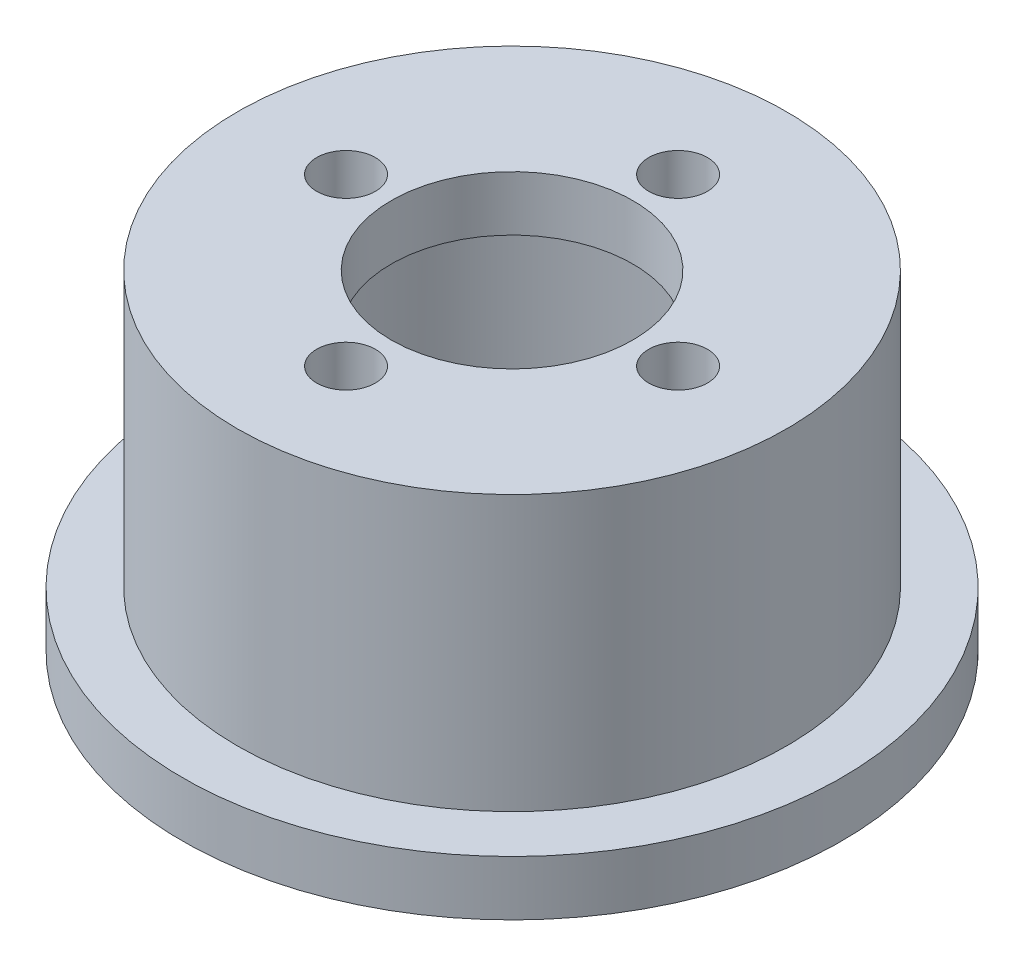
SolidWorks part; units mm, degrees
other "Markup1"
sketch "Sketch5" plane through (-30, 25, 30) normal (-0.0255, 0.5913, 0.806) x (0.9947, 0.0957, -0.0387)
ref_plane "Front Plane" through (0, 0, 0) normal (0, 0, 1) x (1, 0, 0)
ref_plane "Top Plane" through (0, 0, 0) normal (0, 1, 0) x (1, 0, 0)
ref_plane "Right Plane" through (0, 0, 0) normal (1, 0, 0) x (0, 0, -1)
sketch "Sketch1" plane through (0, 0, 0) normal (0, 1, 0) x (1, 0, 0)
  circle A0 centre (0, 0) radius 25
  circle A1 centre (0, 0) radius 20
  dimension "D2" = 50
  dimension "D1" = 40
extrude "Boss-Extrude1" add sketch "Sketch1" along normal blind 20
ref_plane "Plane1" through (0, 20, 0) normal (0, 1, 0) x (1, 0, 0)
sketch "Sketch2" plane through (0, 20, 0) normal (0, 1, 0) x (1, 0, 0)
  circle A0 centre (0, 0) radius 11
  circle A1 centre (0, 0) radius 25
  dimension "D1" = 22
  dimension "D2" = 50
extrude "Boss-Extrude2" add sketch "Sketch2" along normal blind 5
ref_plane "Plane2" through (0, 0, 0) normal (0, -1, 0) x (-1, 0, 0)
sketch "Sketch4" plane through (0, 0, 0) normal (0, -1, 0) x (-1, 0, 0)
  circle A0 centre (0, 0) radius 30
  circle A1 centre (0, 0) radius 20
  dimension "D1" = 40
  dimension "D2" = 60
extrude "Boss-Extrude3" add sketch "Sketch4" along normal blind 5
sketch "Sketch8" plane through (0, 20, 0) normal (0, 1, 0) x (1, 0, 0)
  circle A0 centre (0, -15.1132) radius 2.6722
  circle A1 centre (-15.1132, 0) radius 2.6722
  circle A2 centre (0, 15.1132) radius 2.6722
  circle A3 centre (15.1132, 0) radius 2.6722
  point P11 (0, 0)
  dimension "D1" = 4
extrude "Cut-Extrude2" cut sketch "Sketch8" along normal blind 10
equation "\"BallBearingDiameter\"= 22mm"
equation "\"D1@Sketch2\"=\"BallBearingDiameter\""
equation "\"SmallTubeOD\"= 50mm"
equation "\"SmallTubeID\"= \"SmallTubeOD\" - \"WallThickness\" * 2"
equation "\"D1@Sketch1\"=\"SmallTubeID\""
equation "\"D2@Sketch1\"=\"SmallTubeOD\""
equation "\"D2@Sketch2\"=\"SmallTubeOD\""
equation "\"ZTravel\"= 20mm"
equation "\"WallThickness\"= 5mm"
equation "\"D1@Boss-Extrude2\"=\"WallThickness\""
equation "\"D1@Boss-Extrude1\"=\"ZTravel\""
equation "\"D1@Sketch4\"=\"SmallTubeID\""
equation "\"RestrictingFlangeOD\"= \"SmallTubeOD\" + 10mm"
equation "\"D2@Sketch4\"=\"RestrictingFlangeOD\""
equation "\"D1@Boss-Extrude3\"=\"WallThickness\""
